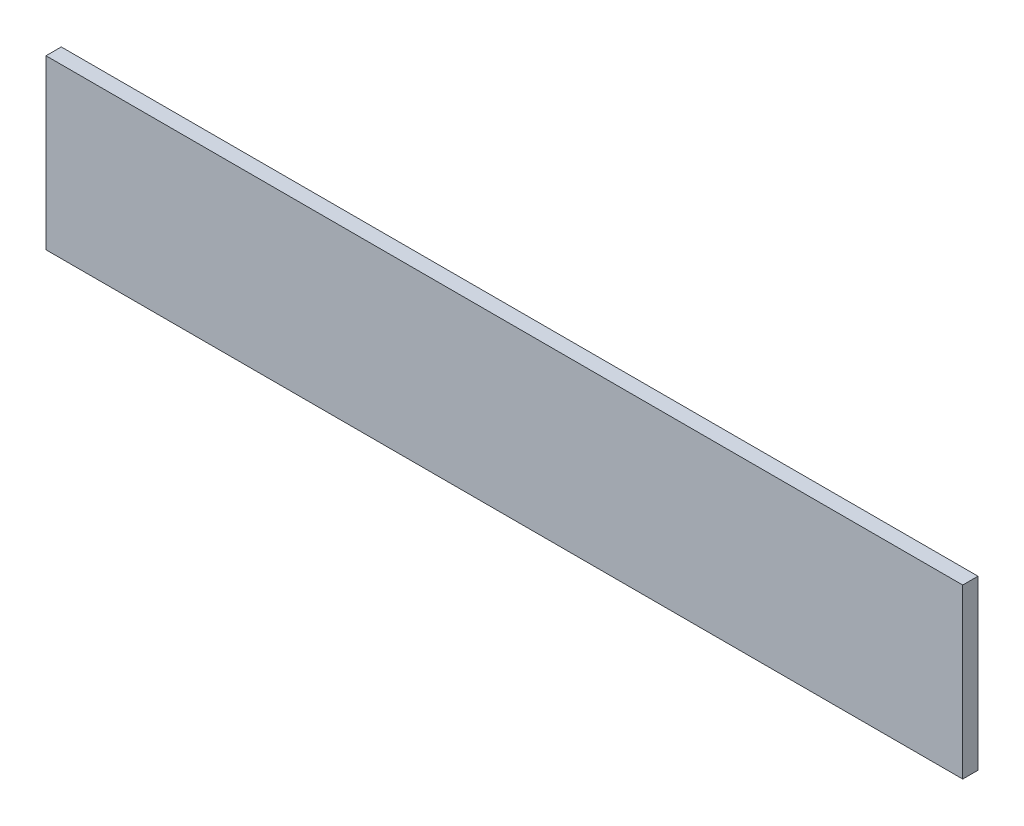
SolidWorks part; units mm, degrees
ref_plane "Plan de face" through (0, 0, 0) normal (0, 0, 1) x (1, 0, 0)
ref_plane "Plan de dessus" through (0, 0, 0) normal (0, 1, 0) x (1, 0, 0)
ref_plane "Plan de droite" through (0, 0, 0) normal (1, 0, 0) x (0, 0, -1)
sketch "Esquisse1" plane through (0, 0, 0) normal (0, 0, 1) x (1, 0, 0)
  line L1 (0, 0) -> (600, 0)
  line L2 (0, 0) -> (0, 110)
  line L3 (0, 110) -> (600, 110)
  line L4 (600, 0) -> (600, 110)
  dimension "D1" = 600
  dimension "D2" = 110
extrude "Boss.-Extru.1" add sketch "Esquisse1" along normal blind 10
